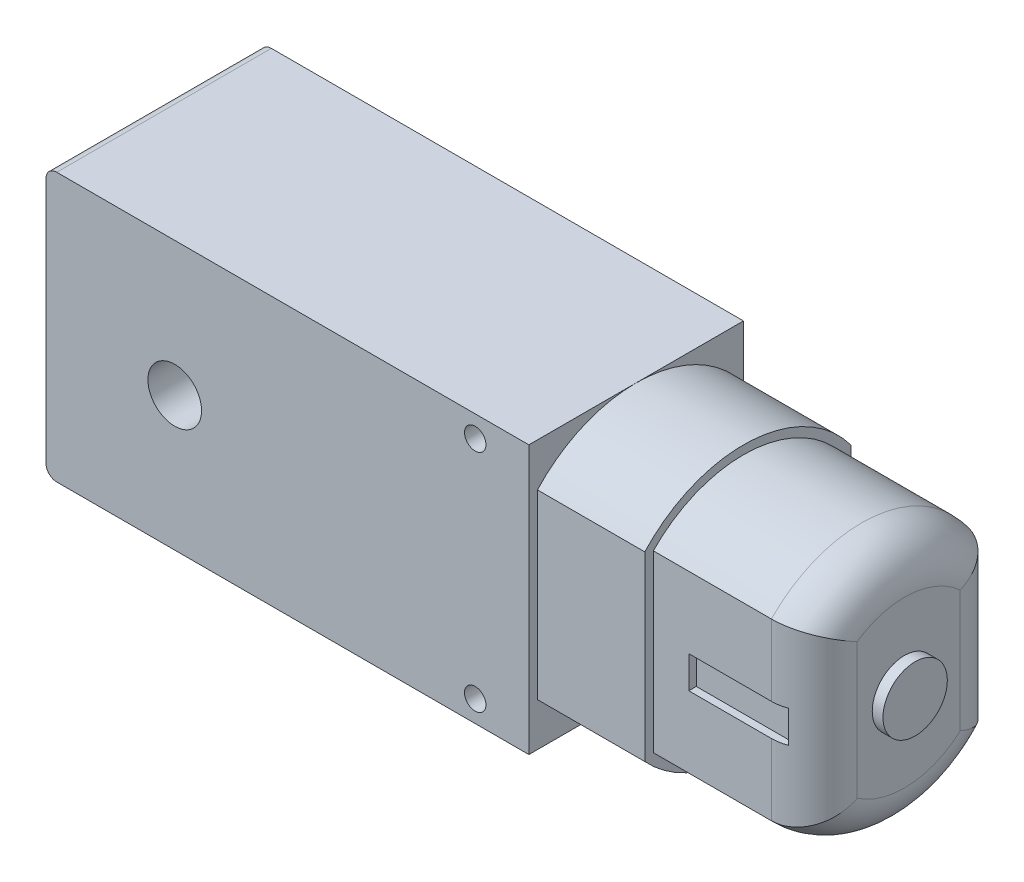
SolidWorks part; units mm, degrees
ref_plane "Front Plane" through (0, 0, 0) normal (0, 0, 1) x (1, 0, 0)
ref_plane "Top Plane" through (0, 0, 0) normal (0, 1, 0) x (1, 0, 0)
ref_plane "Right Plane" through (0, 0, 0) normal (1, 0, 0) x (0, 0, -1)
sketch "Sketch1" plane through (0, 0, 0) normal (0, 0, 1) x (1, 0, 0)
  line L1 (35, -12.5) -> (-35, -12.5)
  line L2 (35, -12.5) -> (35, 12.5)
  line L3 (35, 12.5) -> (-35, 12.5)
  line L4 (-35, -12.5) -> (-35, 12.5)
  line L5 (35, -12.5) -> (-35, 12.5) construction
  line L6 (35, 12.5) -> (-35, -12.5) construction
  point P0 (0, 0)
  dimension "D1" = 70
  dimension "D2" = 25
extrude "Boss-Extrude1" add sketch "Sketch1" along normal mid plane 20
sketch "Sketch2" plane through (35, 0, 0) normal (1, 0, 0) x (0, 0, -1)
  line L1 (-10, -7.5) -> (-10, -12.5)
  line L2 (10, 7.5) -> (10, 12.5)
  line L5 (10, -12.5) -> (10, 12.5)
  line L6 (10, 12.5) -> (-10, 12.5)
  line L7 (-10, 12.5) -> (-10, -12.5)
  line L8 (-10, -12.5) -> (10, -12.5)
  line L9 (10, -12.5) -> (10, -7.5)
  line L10 (10, 12.5) -> (-10, 12.5)
  line L11 (-10, 12.5) -> (-10, 7.5)
  line L12 (-10, -12.5) -> (10, -12.5)
  arc A0 (-10, -7.5) -> (10, -7.5) centre (0, 0) ccw
  arc A1 (10, 7.5) -> (-10, 7.5) centre (0, 0) ccw
  line M6 (10, -12.5) -> (10, 12.5)
  line M7 (10, 12.5) -> (-10, 12.5)
  line M8 (-10, 12.5) -> (-10, -12.5)
  line M9 (-10, -12.5) -> (10, -12.5)
  dimension "D1" = 0
extrude "Cut-Extrude2" cut sketch "Sketch2" against normal blind 25 contours A1 L10 M8 | A1 M6 M7 | A0 L12 M6 | A0 M8 M9 region at (35, -11.0705, 7.611) region at (35, 11.0705, 7.611) region at (35, -11.0705, -7.611) region at (35, 11.0705, -7.611)
sketch "Sketch4" plane through (35, 0, 0) normal (1, 0, 0) x (0, 0, -1)
  line L0 (-9.2, 8.4623) -> (-9.2, -8.4623)
  line L1 (-10, -7.5) -> (-10, 7.5) construction
  line L2 (-9.2, 8.4623) -> (-11.6207, 8.4623)
  line L3 (-11.6207, 8.4623) -> (-11.6207, -8.4623)
  line L4 (-11.6207, -8.4623) -> (-9.2, -8.4623)
  arc A0 (10, 7.5) -> (-10, 7.5) centre (0, 0) ccw construction
  arc A1 (-10, -7.5) -> (10, -7.5) centre (0, 0) ccw construction
  dimension "D1" = 0.8
extrude "Cut-Extrude3" cut sketch "Sketch4" against normal blind 25
sketch "Sketch5" plane through (35, 0, 0) normal (1, 0, 0) x (0, 0, -1)
  line L2 (-8.4, 8.1443) -> (-8.4, -8.1443)
  line L3 (9.2, -7.2284) -> (9.2, 7.2284)
  line L4 (-9.2, 8.4623) -> (-9.2, -8.4623)
  line L5 (10, -7.5) -> (10, 7.5)
  line L6 (-9.2, 8.4623) -> (-9.2, -8.4623)
  line L7 (10, -7.5) -> (10, 7.5)
  arc A2 (9.2, 7.2284) -> (-8.4, 8.1443) centre (0, 0) ccw
  arc A3 (-8.4, -8.1443) -> (9.2, -7.2284) centre (0, 0) ccw
  arc A4 (10, 7.5) -> (-9.2, 8.4623) centre (0, 0) ccw
  arc A5 (-9.2, -8.4623) -> (10, -7.5) centre (0, 0) ccw
  arc A6 (10, 7.5) -> (-9.2, 8.4623) centre (0, 0) ccw
  arc A7 (-9.2, -8.4623) -> (10, -7.5) centre (0, 0) ccw
  dimension "D1" = 0
  dimension "D2" = 0.8
extrude "Cut-Extrude4" cut sketch "Sketch5" against normal blind 15
fillet "Fillet1" radius 4 4 edges at (35, 0, -9.2) (35, -11.6842, -0.608) (35, 0, 8.4) (35, 11.6842, -0.608)
sketch "Sketch6" plane through (35, 0, 0) normal (1, 0, 0) x (0, 0, -1)
  circle A0 centre (0, 0) radius 3
  dimension "D1" = 6
extrude "Boss-Extrude2" add sketch "Sketch6" along normal blind 1
sketch "Sketch7" plane through (0, 0, -9.2) normal (0, 0, -1) x (-1, 0, 0)
  line L0 (-31, 7.2284) -> (-31, -7.2284) construction
  line L1 (-32.3651, -1.5) -> (-23.3004, -1.5)
  line L2 (-32.3651, -1.5) -> (-32.3651, 1.5)
  line L3 (-32.3651, 1.5) -> (-23.3004, 1.5)
  line L4 (-23.3004, -1.5) -> (-23.3004, 1.5)
  point P6 (-31, 0)
  point P7 (-23.3004, 0)
  dimension "D1" = 3
extrude "Cut-Extrude5" cut sketch "Sketch7" against normal blind 1.5
mirror "Mirror1" about plane through (0, 0, 0) normal (0, 0, 1) of "Cut-Extrude5"
fillet "Fillet2" radius 1 2 edges at (-35, 12.5, 0) (-35, -12.5, 0)
sketch "Sketch8" plane through (0, 0, 0) normal (0, 0, 1) x (1, 0, 0)
  line L0 (-35, 11.5) -> (-35, -11.5) construction
  line L1 (-35, -2.5) -> (-40, -2.5)
  line L2 (-35, -2.5) -> (-35, 2.5)
  line L3 (-35, 2.5) -> (-40, 2.5)
  line L4 (-40, -2.5) -> (-40, 2.5)
  circle A0 centre (-37.5, 0) radius 1.5
  point P6 (-40, 0)
  dimension "D3" = 3
  dimension "D1" = 5
  dimension "D2" = 5
extrude "Boss-Extrude3" add sketch "Sketch8" along normal mid plane 3.5
sketch "Sketch9" plane through (0, 0, 10) normal (0, 0, 1) x (1, 0, 0)
  line L0 (8.2693, 0) -> (-21.3687, 0) construction
  line L1 (-34, -12.5) -> (10, -12.5) construction
  line L2 (-35, 11.5) -> (-35, -11.5) construction
  circle A0 centre (5, -10.5) radius 1
  circle A1 centre (5, 10.5) radius 1
  dimension "D1" = 2
  dimension "D2" = 2
  dimension "D3" = 40
extrude "Cut-Extrude7" cut sketch "Sketch9" along normal through all and the other way through all
sketch "Sketch10" plane through (0, 0, -10) normal (0, 0, -1) x (-1, 0, 0)
  line L0 (35, 11.5) -> (35, -11.5) construction
  circle A0 centre (23, 0) radius 2.5
  dimension "D2" = 5
  dimension "D1" = 12
extrude "Cut-Extrude8" cut sketch "Sketch10" against normal through all
